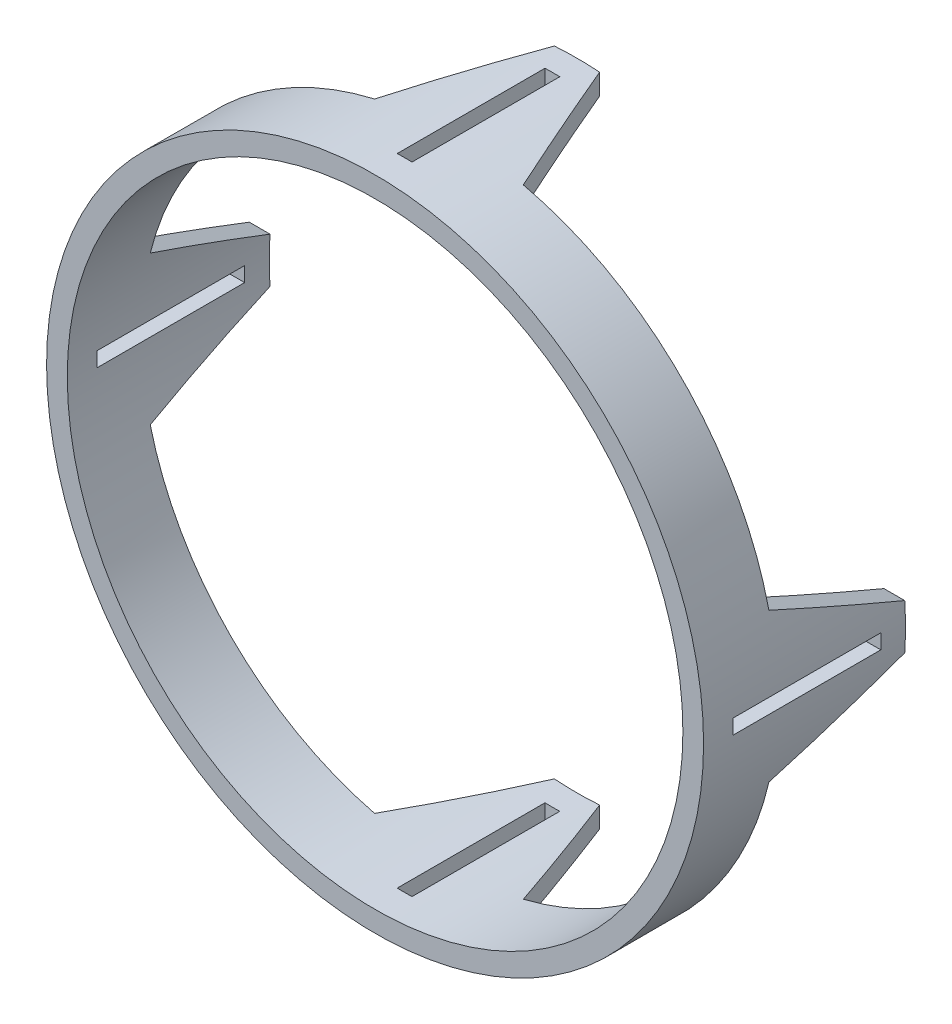
SolidWorks part; units mm, degrees
ref_plane "Front Plane" through (0, 0, 0) normal (0, 0, 1) x (1, 0, 0)
ref_plane "Top Plane" through (0, 0, 0) normal (0, 1, 0) x (1, 0, 0)
ref_plane "Right Plane" through (0, 0, 0) normal (1, 0, 0) x (0, 0, -1)
sketch "Sketch1" plane through (0, 0, 0) normal (0, 0, 1) x (1, 0, 0)
  circle A0 centre (0, 0) radius 79.375
  circle A1 centre (0, 0) radius 84.709
  dimension "D1" = 158.75
  dimension "D2" = 169.418
extrude "Boss-Extrude1" add sketch "Sketch1" along normal blind 19.05
sketch "Sketch3" plane through (0, 0, 0) normal (0, 0, -1) x (-1, 0, 0)
  line L0 (30.8173, 0) -> (-22.3005, 0) construction
  line L1 (0, -12.9993) -> (0, 95.4691) construction
  line L2 (-5.715, 79.169) -> (-5.715, 84.516)
  line L3 (5.715, 79.169) -> (5.715, 84.516)
  line L4 (-5.715, -79.169) -> (-5.715, -84.516)
  line L5 (5.715, -79.169) -> (5.715, -84.516)
  line L6 (0, 0) -> (44.2484, -44.2484) construction
  line L7 (79.169, -5.715) -> (84.516, -5.715)
  line L8 (79.169, 5.715) -> (84.516, 5.715)
  line L9 (-79.169, 5.715) -> (-84.516, 5.715)
  line L10 (-79.169, -5.715) -> (-84.516, -5.715)
  arc A0 (5.715, 79.169) -> (-5.715, 79.169) centre (0, 0) ccw
  circle A2 centre (0, 0) radius 79.375 construction
  arc A3 (5.715, 84.516) -> (-5.715, 84.516) centre (0, 0) ccw
  circle A4 centre (0, 0) radius 84.709 construction
  arc A5 (5.715, -79.169) -> (-5.715, -79.169) centre (0, 0) cw
  arc A6 (5.715, -84.516) -> (-5.715, -84.516) centre (0, 0) cw
  arc A7 (84.516, -5.715) -> (84.516, 5.715) centre (0, 0) ccw
  arc A8 (79.169, -5.715) -> (79.169, 5.715) centre (0, 0) ccw
  arc A9 (-79.169, -5.715) -> (-79.169, 5.715) centre (0, 0) cw
  arc A10 (-84.516, -5.715) -> (-84.516, 5.715) centre (0, 0) cw
  dimension "D1" = 5.715
  dimension "D2" = 5.715
  dimension "D3" = 5.715
  dimension "D4" = 5.715
  dimension "D5" = 45
extrude "Boss-Extrude2" add sketch "Sketch3" along normal blind 33.02
sketch "Sketch2" plane through (0, 0, 0) normal (0, 1, 0) x (1, 0, 0)
  line L0 (5.715, 33.02) -> (-5.715, 33.02) construction
  line L1 (0, -2.0807) -> (0, -15.8358) construction
  line L3 (-1.905, -11.43) -> (1.905, -11.43)
  line L4 (-1.905, -11.43) -> (-1.905, 26.67)
  line L5 (-1.905, 26.67) -> (1.905, 26.67)
  line L6 (1.905, -11.43) -> (1.905, 26.67)
  line L7 (-1.905, -11.43) -> (1.905, 26.67) construction
  line L8 (-1.905, 26.67) -> (1.905, -11.43) construction
  point P0 (0, 7.62)
  point P10 (0, 33.02)
  dimension "D1" = 3.81
  dimension "D2" = 38.1
  dimension "D3" = 6.35
ref_axis "Axis1" through (0, 0, 2.0807) along (0, 0, 1)
extrude "Cut-Extrude1" cut sketch "Sketch2" against normal through all
pattern_circular "CirPattern1" count 4 over 360 about axis through (0, 0, 2.0807) along (0, 0, 1) of "Cut-Extrude1"
chamfer "Chamfer1" distance 13.462 angle 68 8 edges at (-5.715, 81.8425, 0) (5.715, 81.8425, 0) (-5.715, -81.8425, 0) (5.715, -81.8425, 0) (-81.8425, -5.715, 0) (81.8425, -5.715, 0) (81.8425, 5.715, 0) (-81.8425, 5.715, 0) first distance on face at (-50.8956, 50.8956, 0) first distance on face at (50.8956, 50.8956, 0) first distance on face at (-50.8956, -50.8956, 0) first distance on face at (50.8956, -50.8956, 0)
